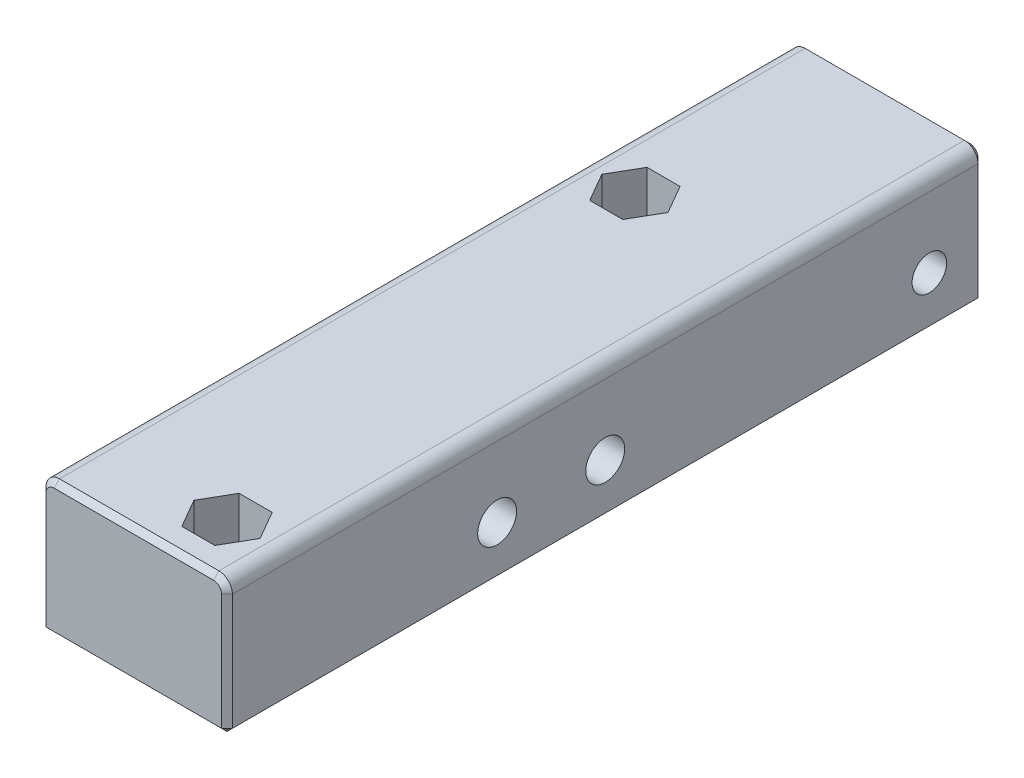
SolidWorks part; units mm, degrees
ref_plane "Front Plane" through (0, 0, 0) normal (0, 0, 1) x (1, 0, 0)
ref_plane "Top Plane" through (0, 0, 0) normal (0, 1, 0) x (1, 0, 0)
ref_plane "Right Plane" through (0, 0, 0) normal (1, 0, 0) x (0, 0, -1)
sketch "Sketch1" plane through (0, 0, 0) normal (0, 0, 1) x (1, 0, 0)
  line L1 (0, 0) -> (21.9075, 0)
  line L2 (0, 0) -> (0, 15.875)
  line L3 (0, 15.875) -> (21.9075, 15.875)
  line L4 (21.9075, 0) -> (21.9075, 15.875)
  dimension "D1" = 21.9075
  dimension "D2" = 15.875
extrude "Boss-Extrude1" add sketch "Sketch1" along normal blind 101.6
fillet "Fillet1" radius 1.5875 2 edges at (21.9075, 15.875, 50.8) (0, 15.875, 50.8)
sketch "Sketch2" plane through (21.9075, 0, 0) normal (1, 0, 0) x (0, 0, -1)
  line L0 (-101.6, 6.0452) -> (0, 6.0452) construction
  line L1 (-101.6, 0) -> (-101.6, 14.2875) construction
  line L2 (0, 0) -> (0, 14.2875) construction
  line L3 (-101.6, 0) -> (0, 0) construction
  circle A4 centre (-57.15, 6.0452) radius 2.286
  circle A11 centre (-44.45, 6.0452) radius 2.286
  circle A12 centre (-6.35, 6.0452) radius 2.032
  dimension "D1" = 6.0452
  dimension "D2" = 4.572
  dimension "D3" = 4.064
  dimension "D6" = 6.35
  dimension "D4" = 12.7
  dimension "D5" = 38.1
extrude "Cut-Extrude2" cut sketch "Sketch2" against normal through all contours A4 L0 | L0 A4 | L0 A11 | A11 L0 | L0 A12 | A12 L0 region at (21.9075, 7.0154, 57.15) region at (21.9075, 6.9076, 6.35) region at (21.9075, 5.1828, 6.35) region at (21.9075, 7.0154, 44.45) region at (21.9075, 5.075, 44.45) region at (21.9075, 5.075, 57.15)
sketch "Sketch3" plane through (0, 0, 0) normal (0, -1, 0) x (1, 0, 0)
  line L0 (0, 101.6) -> (21.9075, 101.6) construction
  line L1 (17.5006, 85.9155) -> (13.6144, 85.9155)
  line L2 (13.6144, 85.9155) -> (11.6714, 82.55)
  line L3 (11.6714, 82.55) -> (13.6144, 79.1845)
  line L4 (13.6144, 79.1845) -> (17.5006, 79.1845)
  line L5 (17.5006, 79.1845) -> (19.4436, 82.55)
  line L6 (19.4436, 82.55) -> (17.5006, 85.9155)
  line L7 (8.2931, 28.7655) -> (4.4069, 28.7655)
  line L8 (4.4069, 28.7655) -> (2.4639, 25.4)
  line L9 (2.4639, 25.4) -> (4.4069, 22.0345)
  line L10 (4.4069, 22.0345) -> (8.2931, 22.0345)
  line L11 (8.2931, 22.0345) -> (10.2361, 25.4)
  line L12 (10.2361, 25.4) -> (8.2931, 28.7655)
  line L13 (21.9075, 101.6) -> (21.9075, 0) construction
  line L14 (0, 101.6) -> (0, 0) construction
  line L15 (0, 0) -> (21.9075, 0) construction
  circle A4 centre (15.5575, 82.55) radius 3.3655 construction
  circle A5 centre (6.35, 25.4) radius 3.3655 construction
  dimension "D1" = 6.731
  dimension "D2" = 6.731
  dimension "D3" = 19.05
  dimension "D4" = 6.35
  dimension "D5" = 6.35
  dimension "D6" = 25.4
extrude "Cut-Extrude3" cut sketch "Sketch3" against normal up to next contours L11 L12 L7 L8 L9 L10 | L5 L6 L1 L2 L3 L4 region at (15.5575, 0, 82.55) region at (6.35, 0, 25.4)
sketch "Sketch5" plane through (0, 0, 101.6) normal (0, 0, 1) x (1, 0, 0)
  line L0 (21.9075, 0) -> (21.9075, 14.2875) construction
  line L1 (0, 0) -> (21.9075, 0)
  line L2 (0, 0) -> (0, 15.875)
  line L3 (0, 15.875) -> (21.9075, 15.875)
  line L4 (21.9075, 0) -> (21.9075, 15.875)
  dimension "D1" = 15.875
extrude "Cut-Extrude5" cut sketch "Sketch5" against normal blind 12.7 contours L3 L4 L1 L2
chamfer "Chamfer1" distance 0.635 angle 45 14 edges at (0, 7.1437, 0) (0, 7.1437, 88.9) (0.465, 15.41, 0) (0.465, 15.41, 88.9) (10.9537, 15.875, 0) (10.9537, 15.875, 88.9) (21.4425, 15.41, 0) (21.4425, 15.41, 88.9) (21.9075, 7.1437, 0) (21.9075, 7.1437, 88.9) (10.9537, 0, 0) (0, 0, 44.45) (21.9075, 0, 44.45) (10.9537, 0, 88.9)
chamfer "Chamfer2" distance 1.27 angle 45 12 edges at (3.4354, 0, 27.0828) (3.4354, 0, 23.7173) (6.35, 0, 22.0345) (9.2646, 0, 23.7173) (9.2646, 0, 27.0828) (6.35, 0, 28.7655) (15.5575, 0, 85.9155) (12.6429, 0, 84.2327) (12.6429, 0, 80.8672) (15.5575, 0, 79.1845) (18.4721, 0, 84.2327) (18.4721, 0, 80.8672)
